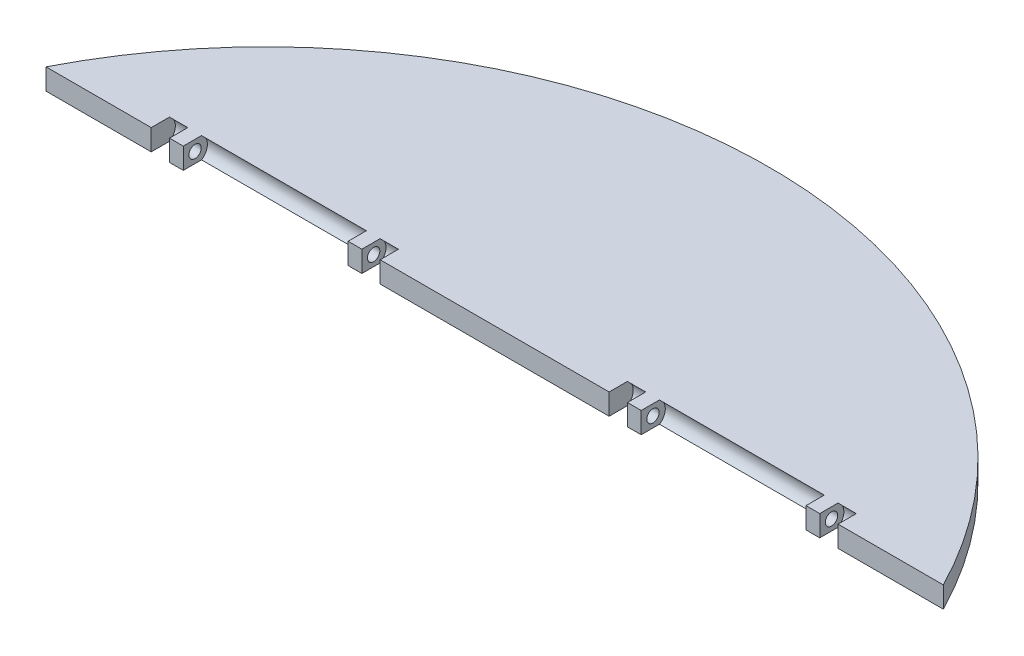
SolidWorks part; units mm, degrees
ref_plane "Front Plane" through (0, 0, 0) normal (0, 0, 1) x (1, 0, 0)
ref_plane "Top Plane" through (0, 0, 0) normal (0, 1, 0) x (1, 0, 0)
ref_plane "Right Plane" through (0, 0, 0) normal (1, 0, 0) x (0, 0, -1)
sketch "Sketch1" plane through (0, 0, 0) normal (0, 1, 0) x (1, 0, 0)
  line L0 (-55, 0) -> (55, 0) construction
  line L1 (-48.9898, 25) -> (48.9898, 25)
  circle A0 centre (0, 0) radius 55
  dimension "D1" = 110
  dimension "D2" = 25
extrude "Boss-Extrude1" add sketch "Sketch1" along normal blind 2.3 contours L1 A0 region at (0, 0, -37.3339)
sketch "Sketch2" plane through (0, 0, 0) normal (1, 0, 0) x (0, 0, -1)
  line L0 (25, 2.3) -> (25, 0) construction
  line L1 (25, 0) -> (26.9919, 0)
  line L2 (25, 2.3) -> (25, 0)
  line L4 (25, 2.3) -> (26.9919, 2.3)
  line L5 (55, 2.3) -> (25, 2.3) construction
  line L7 (26.9919, 2.3) -> (25, 2.3)
  circle A0 centre (26.2848, 1.15) radius 0.675
  arc A2 (26.9919, 0) -> (26.9919, 2.3) centre (26.2848, 1.15) ccw
  point P3 (25, 1.15)
  dimension "D1" = 1.35
  dimension "D2" = 1.35
  dimension "D3" = 1.2848
extrude "Cut-Extrude1" cut sketch "Sketch2" against normal mid plane 25 from offset 25 contours A0 | L1 A2 L4 L2 A0 region at (0, 1.15, -25.035) region at (0, 1.15, -26.2848)
extrude "Boss-Extrude2" add sketch "Sketch2<8>" along normal blind 1.5 from offset 34 contours L1 A2 L4 L2 A0 region at (0, 1.15, -25.035)
sketch "Sketch2<8>" plane through (0, 0, 0) normal (1, 0, 0) x (0, 0, -1) same geometry as "Sketch2"
extrude "Boss-Extrude5" add sketch "Sketch2<11>" along normal blind 1.5 from offset 14.5 contours L1 A2 L4 L2 A0 region at (0, 1.15, -25.035)
sketch "Sketch2<11>" plane through (0, 0, 0) normal (1, 0, 0) x (0, 0, -1) same geometry as "Sketch2"
mirror "Mirror1" about plane through (0, 0, 0) normal (1, 0, 0) of "Boss-Extrude5", "Cut-Extrude1", "Boss-Extrude2"
sketch "Sketch4" plane through (0, 0, 0) normal (1, 0, 0) x (0, 0, -1)
  line L0 (25, 0) -> (55, 0) construction
  line L1 (25, 0) -> (55, 0)
  line L2 (38.875, -1.8) -> (38.875, 0)
  line L3 (41.125, -1.8) -> (41.125, 0)
  circle A0 centre (40, -1.8) radius 0.825
  arc A1 (38.875, -1.8) -> (41.125, -1.8) centre (40, -1.8) ccw
  point P5 (40, 0)
  dimension "D1" = 1.65
  dimension "D3" = 0.3
  dimension "D2" = 1.8
extrude "Boss-Extrude3" add sketch "Sketch4" along normal mid plane 2 from offset 10.5 contours L2 A1 L3 L1 A0 region at (0, -0.0369, -40)
